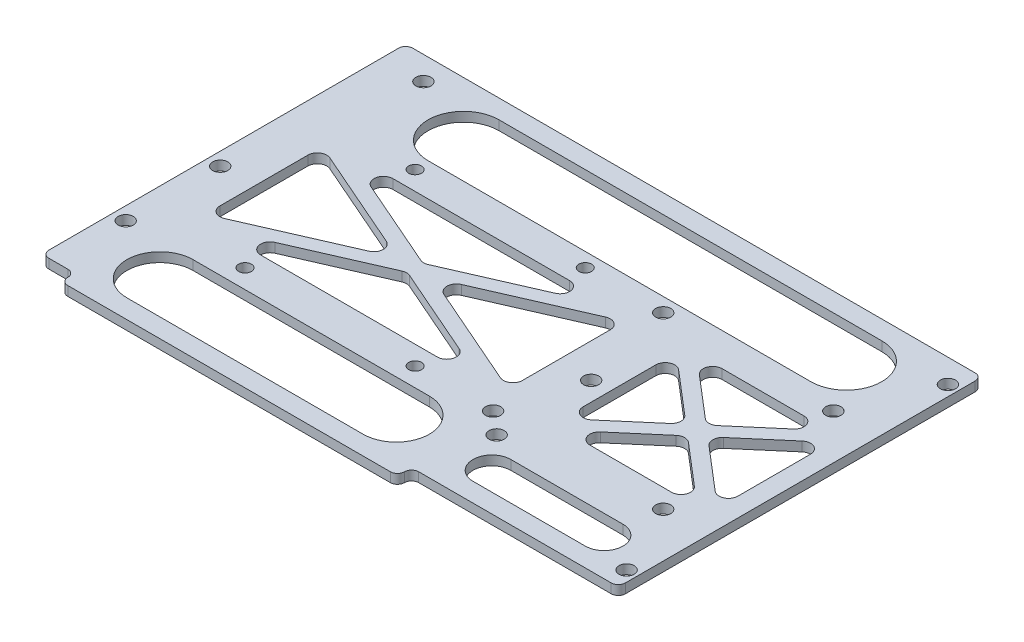
SolidWorks part; units mm, degrees
material "A-玻璃纤维"
ref_plane "前视基准面" through (0, 0, 0) normal (0, 0, 1) x (1, 0, 0)
ref_plane "上视基准面" through (0, 0, 0) normal (0, 1, 0) x (1, 0, 0)
ref_plane "右视基准面" through (0, 0, 0) normal (1, 0, 0) x (0, 0, -1)
other "Configuration Table"
sketch "草图1" plane through (0, 0, 0) normal (0, 1, 0) x (1, 0, 0)
  line L1 (-18, 18) -> (18, 18) construction
  line L2 (-18, 18) -> (-18, -18) construction
  line L3 (-18, -18) -> (18, -18) construction
  line L4 (18, 18) -> (18, -18) construction
  line L5 (-18, 18) -> (18, -18) construction
  line L6 (-18, -18) -> (18, 18) construction
  line L13 (-50, 40) -> (50, 40)
  line L14 (-50, 40) -> (-50, -40)
  line L15 (-50, -40) -> (50, -40)
  line L16 (50, 40) -> (50, -40)
  circle A0 centre (18, -18) radius 1.35
  circle A1 centre (-18, -18) radius 1.35
  circle A2 centre (-18, 18) radius 1.35
  circle A3 centre (18, 18) radius 1.35
  point P0 (0, 0)
  point P19 (-50, 0)
  dimension "D2" = 2.7
  dimension "D1" = 36
  dimension "D3" = 100
  dimension "D7" = 80
  dimension "D8" = 50
extrude "凸台-拉伸1" add sketch "草图1" along normal blind 2
sketch "草图2" plane through (0, 2, 0) normal (0, 1, 0) x (1, 0, 0)
  line L0 (-50, -40) -> (50, -40) construction
  line L1 (-50, 40) -> (-42, 40)
  line L2 (-50, 40) -> (-50, -40)
  line L3 (-50, -40) -> (-42, -40)
  line L4 (-42, 40) -> (-42, -40)
  dimension "D1" = 8
extrude "切除-拉伸1" cut sketch "草图2" against normal blind 5
sketch "草图3" plane through (0, 2, 0) normal (0, 1, 0) x (1, 0, 0)
  line L0 (-39.25, -22) -> (-39.25, -2) construction
  line L1 (-42, -40) -> (-42, 40) construction
  line L2 (-42, -40) -> (50, -40) construction
  line L3 (0, -47.9141) -> (0, 17.5419) construction
  circle A0 centre (-39.25, -22) radius 1.6
  circle A1 centre (-39.25, -2) radius 1.6
  circle A4 centre (39.25, -22) radius 1.6
  circle A5 centre (39.25, -2) radius 1.6
  dimension "D3" = 3.2
  dimension "D1" = 20
  dimension "D2" = 2.75
  dimension "D4" = 18
  dimension "D5" = 78.5
extrude "切除-拉伸2" cut sketch "草图3" against normal blind 5
sketch "草图4" plane through (0, 2, 0) normal (0, 1, 0) x (1, 0, 0)
  line L1 (50, 40) -> (80, 40)
  line L2 (50, 40) -> (50, -40)
  line L3 (50, -40) -> (80, -40)
  line L4 (80, 40) -> (80, -40)
  dimension "D1" = 30
extrude "凸台-拉伸2" add sketch "草图4" against normal blind 2
sketch "草图5" plane through (0, 2, 0) normal (0, 1, 0) x (1, 0, 0)
  line L0 (80, -40) -> (80, 40) construction
  line L1 (34.5, 18) -> (70.5, 18) construction
  line L2 (34.5, 18) -> (34.5, -18) construction
  line L3 (34.5, -18) -> (70.5, -18) construction
  line L4 (70.5, 18) -> (70.5, -18) construction
  circle A0 centre (34.5, -18) radius 1.6
  circle A1 centre (70.5, -18) radius 1.6
  circle A2 centre (70.5, 18) radius 1.6
  circle A3 centre (34.5, 18) radius 1.6
  point P4 (34.5, 0)
  dimension "D2" = 3.2
  dimension "D1" = 36
  dimension "D3" = 45.5
extrude "切除-拉伸3" cut sketch "草图5" against normal blind 2
sketch "草图6" plane through (0, 2, 0) normal (0, 1, 0) x (1, 0, 0)
  line L1 (80, -40) -> (36.25, -40)
  line L2 (80, -40) -> (80, -37)
  line L3 (80, -37) -> (36.25, -37)
  line L4 (36.25, -40) -> (36.25, -37)
  line L5 (-42, -40) -> (-35, -40)
  line L6 (-42, -40) -> (-42, -37)
  line L7 (-42, -37) -> (-35, -37)
  line L8 (-35, -40) -> (-35, -37)
  circle A1 centre (39.25, -22) radius 1.6 construction
  dimension "D1" = 3
  dimension "D2" = 3
  dimension "D3" = 7
extrude "切除-拉伸4" cut sketch "草图6" against normal blind 10
sketch "草图8" plane through (0, 2, 0) normal (0, 1, 0) x (1, 0, 0)
  circle A0 centre (77.75, -33) radius 1.6
  circle A1 centre (77.75, 35) radius 1.6
  circle A2 centre (-33.25, 35) radius 1.6
  dimension "D1" = 3.2
extrude "切除-拉伸5" cut sketch "草图8" against normal blind 10
sketch "草图7" plane through (0, 2, 0) normal (0, 1, 0) x (1, 0, 0)
  line L0 (-25, -29) -> (25, -29) construction
  line L1 (-25, -22) -> (25, -22)
  line L2 (-25, -36) -> (25, -36)
  line L3 (45.25, -29) -> (69, -29) construction
  line L4 (45.25, -25) -> (69, -25)
  line L5 (45.25, -33) -> (69, -33)
  line L6 (-35, -40) -> (36.25, -40) construction
  line L7 (80, -37) -> (36.25, -37) construction
  line L8 (-32, 14) -> (32, 14)
  line L9 (-32, 14) -> (-32, -14)
  line L10 (-32, -14) -> (32, -14)
  line L11 (32, 14) -> (32, -14)
  line L12 (-32, 14) -> (32, -14) construction
  line L13 (-32, -14) -> (32, 14) construction
  line L14 (-42, -37) -> (-32, -37) construction
  line L15 (-42, -37) -> (-42, 3) construction
  line L16 (-42, 3) -> (-32, 3) construction
  line L17 (-32, -37) -> (-32, 3) construction
  line L18 (36.25, -2) -> (42.25, -2) construction
  line L19 (36.25, -2) -> (36.25, -42) construction
  line L20 (36.25, -42) -> (42.25, -42) construction
  line L21 (42.25, -2) -> (42.25, -42) construction
  line L22 (36.25, -2) -> (42.25, -42) construction
  line L23 (36.25, -42) -> (42.25, -2) construction
  line L24 (36.25, -42) -> (33.25, -42) construction
  line L25 (36.25, -42) -> (36.25, -2) construction
  line L26 (36.25, -2) -> (33.25, -2) construction
  line L27 (33.25, -42) -> (33.25, -2) construction
  line L28 (43.25, 14) -> (76, 14)
  line L29 (43.25, 14) -> (43.25, -14)
  line L30 (43.25, -14) -> (76, -14)
  line L31 (76, 14) -> (76, -14)
  line L32 (80, -37) -> (80, 40) construction
  line L33 (-18.25, 28.5) -> (62.75, 28.5) construction
  line L34 (-18.25, 36) -> (62.75, 36)
  line L35 (-18.25, 21) -> (62.75, 21)
  line L36 (80, 40) -> (-42, 40) construction
  arc A0 (-25, -22) -> (-25, -36) centre (-25, -29) ccw
  arc A1 (25, -36) -> (25, -22) centre (25, -29) ccw
  arc A2 (45.25, -25) -> (45.25, -33) centre (45.25, -29) ccw
  arc A3 (69, -33) -> (69, -25) centre (69, -29) ccw
  circle A4 centre (18, -18) radius 1.35 construction
  circle A5 centre (70.5, -18) radius 1.6 construction
  circle A6 centre (70.5, 18) radius 1.6 construction
  arc A7 (-18.25, 36) -> (-18.25, 21) centre (-18.25, 28.5) ccw
  arc A8 (62.75, 21) -> (62.75, 36) centre (62.75, 28.5) ccw
  circle A9 centre (18, 18) radius 1.35 construction
  circle A10 centre (77.75, 35) radius 1.6 construction
  circle A11 centre (-33.25, 35) radius 1.6 construction
  point P2 (0, -29)
  point P8 (57.125, -29)
  point P14 (0, 0)
  point P29 (39.25, -22)
  point P41 (22.25, 28.5)
  point P46 (39.25, -2)
  dimension "D1" = 4
  dimension "D2" = 50
  dimension "D3" = 4
  dimension "D4" = 10
  dimension "D5" = 40
  dimension "D6" = 6
  dimension "D7" = 40
  dimension "D8" = 3
  dimension "D9" = 4
  dimension "D10" = 6
  dimension "D11" = 4
  dimension "D12" = 4
  dimension "D13" = 4
  dimension "D14" = 4
  dimension "D15" = 11
  dimension "D16" = 3
  dimension "D17" = 4
  dimension "D18" = 15
  dimension "D19" = 15
extrude "切除-拉伸6" cut sketch "草图7" against normal blind 10
sketch "草图9" plane through (0, 2, 0) normal (0, 1, 0) x (1, 0, 0)
  line L0 (32, -14) -> (-32, 14)
  line L1 (-32, -14) -> (32, 14)
  line L2 (43.25, 14) -> (76, -14)
  line L3 (43.25, -14) -> (76, 14)
extrude "拉伸-薄壁1" add sketch "草图9" against normal blind 2 thin thin type mid plane wall 3
fillet "圆角1" radius 2 24 edges at (-3.7423, 1, 0) (-32, 1, -12.3627) (-32, 1, 12.3627) (0, 1, -1.6373) (28.2577, 1, -14) (-28.2577, 1, -14) (-28.2577, 1, 14) (28.2577, 1, 14) (32, 1, -12.3627) (3.7423, 1, 0) (32, 1, 12.3627) (76, 1, -12.0265) (61.9333, 1, 0) (76, 1, 12.0265) (59.625, 1, 1.9735) (45.5583, 1, 14) (73.6917, 1, 14) (59.625, 1, -1.9735) (73.6917, 1, -14) (45.5583, 1, -14) (43.25, 1, 12.0265) (57.3167, 1, 0) (43.25, 1, -12.0265) (0, 1, 1.6373)
fillet "圆角2" radius 1.5 8 edges at (80, 1, 37) (80, 1, -40) (-42, 1, -40) (-42, 1, 37) (-35, 1, 37) (-35, 1, 40) (36.25, 1, 37) (36.25, 1, 40)
